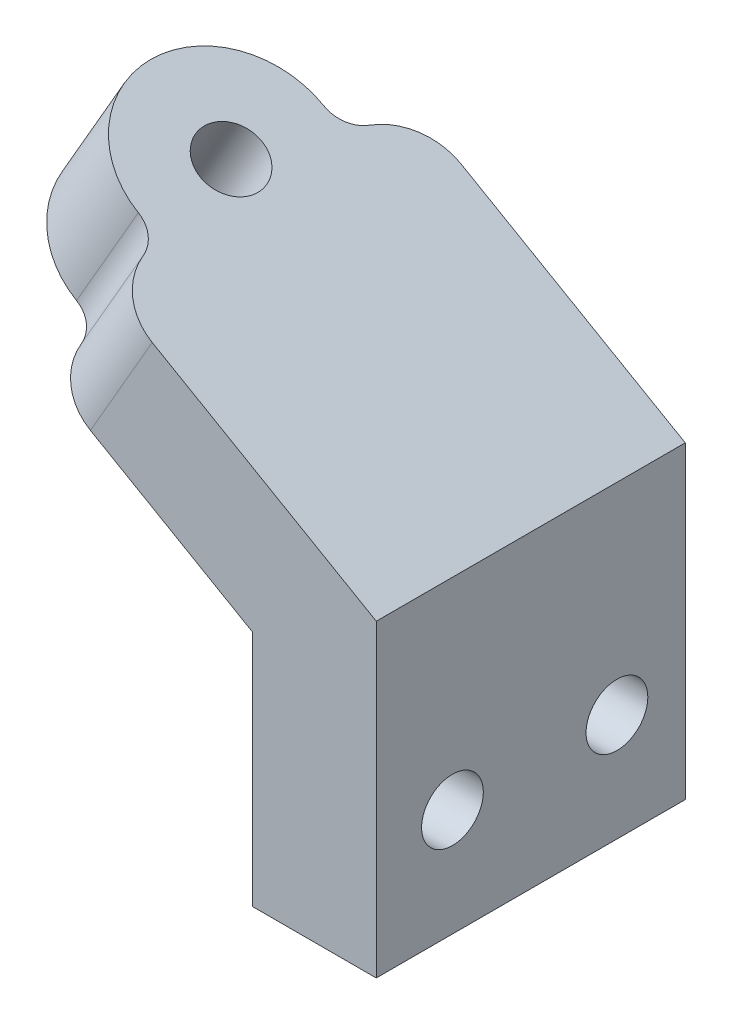
SolidWorks part; units mm, degrees
ref_plane "Front Plane" through (0, 0, 0) normal (0, 0, 1) x (1, 0, 0)
ref_plane "Top Plane" through (0, 0, 0) normal (0, 1, 0) x (1, 0, 0)
ref_plane "Right Plane" through (0, 0, 0) normal (1, 0, 0) x (0, 0, -1)
sketch "Sketch1" plane through (0, 0, 0) normal (0, 0, 1) x (1, 0, 0)
  line L0 (-10, 0) -> (10, 0)
  line L1 (10, 0) -> (10, 50)
  line L2 (10, 50) -> (-52.3538, 86)
  line L3 (-52.3538, 86) -> (-62.3538, 68.6795)
  line L4 (-62.3538, 68.6795) -> (-10, 38.453)
  line L5 (-10, 38.453) -> (-10, 0)
  point P3 (0, 0)
  dimension "D1" = 20
  dimension "D2" = 50
  dimension "D3" = 72
  dimension "D4" = 120
  dimension "D5" = 20
extrude "Boss-Extrude1" add sketch "Sketch1" along normal blind 50
sketch "Sketch2" plane through (24.1506, 41.8301, 0) normal (0.5, 0.866, 0) x (0.866, -0.5, 0)
  line L0 (-88.3397, -50) -> (-88.3397, 0) construction
  line L1 (8.6603, -25) -> (-99.2979, -25) construction
  line L2 (8.6603, -50) -> (8.6603, 0) construction
  line L3 (-16.3397, 0) -> (-88.3397, 0) construction
  line L4 (-16.3397, -50) -> (-88.3397, -50) construction
  line L5 (-72.3397, -50) -> (-88.3397, -50)
  line L6 (-72.3397, 0) -> (-88.3397, 0)
  line L7 (-88.3397, -50) -> (-88.3397, 0)
  arc A0 (-72.3397, -10) -> (-72.3397, -40) centre (-72.3397, -25) ccw
  arc A1 (-72.3397, -10) -> (-72.3397, 0) centre (-72.3397, -5) ccw
  arc A2 (-72.3397, -40) -> (-72.3397, -50) centre (-72.3397, -45) cw
  point P2 (-72.6453, -25)
  point P12 (-66.4003, -5.602)
  dimension "D1" = 30
  dimension "D2" = 10
  dimension "D3" = 81
extrude "Cut-Extrude1" cut sketch "Sketch2" against normal through all
fillet "Fillet1" radius 10 2 edges at (-43.4974, 69.3397, 0) (-43.4974, 69.3397, 50)
hole_wizard "Hole1" positions "Sketch3" profile "Sketch4" legacy end condition through all
sketch "Sketch3" plane through (24.1506, 41.8301, 0) normal (0.5, 0.866, 0) x (0.866, -0.5, 0)
  point P0 (-72.3397, -25)
sketch "Sketch4" plane through (-38.4974, 78, 25) normal (0, 0, 1) x (-0.866, 0.5, 0)
  line L0 (0, 0) -> (0, 79.0452)
  line L1 (0, 79.0452) -> (5, 79.0452)
  line L2 (5, 79.0452) -> (5, 0)
  line L3 (5, 0) -> (0, 0)
  line L4 (0, 110) -> (0, -10) construction
  dimension "Diameter" = 10
  dimension "Depth" = 79.0452
hole_wizard "Hole2" positions "Sketch5" profile "Sketch6" legacy end condition through all
sketch "Sketch5" plane through (10, 0, 0) normal (1, 0, 0) x (0, 0, -1)
  point P0 (-37.6752, 17.3996)
  point P2 (-11.0573, 17.3996)
sketch "Sketch6" plane through (10, 17.3996, 37.6752) normal (0, 1, 0) x (0, 0, -1)
  line L0 (0, 0) -> (0, 71.4878)
  line L1 (0, 71.4878) -> (5, 71.4878)
  line L2 (5, 71.4878) -> (5, 0)
  line L3 (5, 0) -> (0, 0)
  line L4 (0, 110) -> (0, -10) construction
  dimension "Diameter" = 10
  dimension "Depth" = 71.4878
